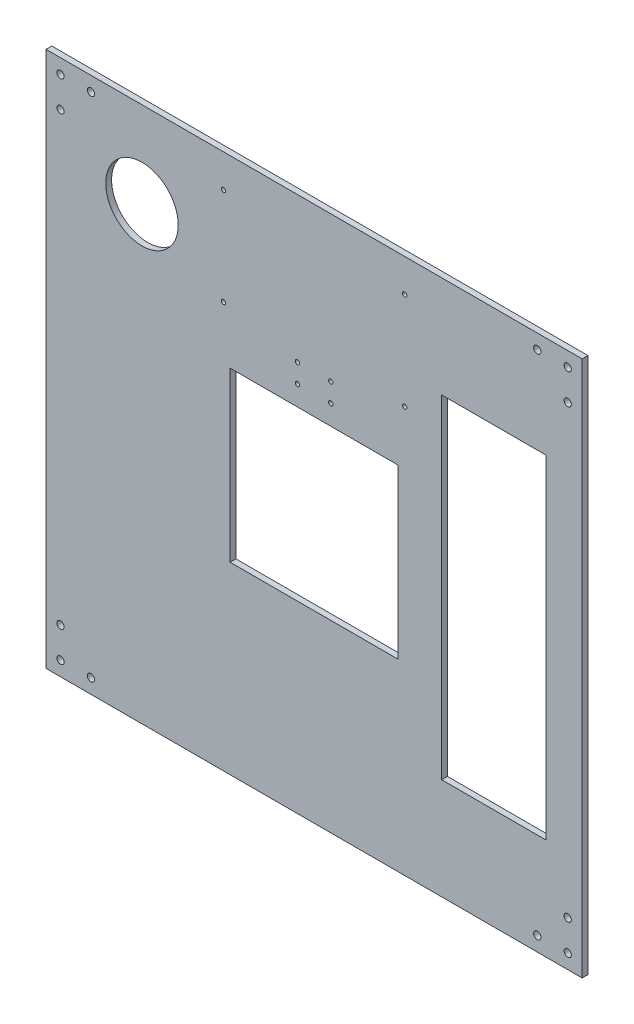
SolidWorks part; units mm, degrees
ref_plane "前视基准面" through (0, 0, 0) normal (0, 0, 1) x (1, 0, 0)
ref_plane "上视基准面" through (0, 0, 0) normal (0, 1, 0) x (1, 0, 0)
ref_plane "右视基准面" through (0, 0, 0) normal (1, 0, 0) x (0, 0, -1)
sketch "草图1" plane through (0, 0, 0) normal (0, 0, 1) x (1, 0, 0)
  line L1 (185, -185) -> (-185, -185)
  line L2 (185, -185) -> (185, 185)
  line L3 (185, 185) -> (-185, 185)
  line L4 (-185, -185) -> (-185, 185)
  line L5 (185, -185) -> (-185, 185) construction
  line L6 (185, 185) -> (-185, -185) construction
  point P0 (0, 0)
  dimension "D1" = 370
  dimension "D2" = 370
extrude "凸台-拉伸1" add sketch "草图1" along normal blind 4
sketch "草图2" plane through (0, 0, 4) normal (0, 0, 1) x (1, 0, 0)
  line L0 (-165, -175) -> (-154, -175) construction
  line L1 (-185, -185) -> (-165, -185) construction
  line L2 (-185, -185) -> (-185, -165) construction
  line L3 (-185, -165) -> (-165, -165) construction
  line L4 (-165, -185) -> (-165, -165) construction
  line L5 (-175, -165) -> (-175, -154) construction
  circle A0 centre (-175, -175) radius 2.5
  circle A1 centre (-154, -175) radius 2.5
  circle A2 centre (-175, -154) radius 2.5
  circle A3 centre (-154, 175) radius 2.5
  circle A4 centre (-175, 154) radius 2.5
  circle A5 centre (-175, 175) radius 2.5
  circle A6 centre (175, 154) radius 2.5
  circle A7 centre (154, 175) radius 2.5
  circle A8 centre (175, 175) radius 2.5
  circle A9 centre (154, -175) radius 2.5
  circle A10 centre (175, -154) radius 2.5
  circle A11 centre (175, -175) radius 2.5
  point P34 (0, 0)
  dimension "D3" = 10
  dimension "D4" = 10
  dimension "D5" = 5
  dimension "D6" = 11
  dimension "D7" = 5
  dimension "D9" = 5
  dimension "D1" = 20
  dimension "D2" = 20
  dimension "D8" = 11
  dimension "D10" = 4
extrude "切除-拉伸1" cut sketch "草图2" against normal through all
sketch "草图6" plane through (0, 0, 0) normal (0, 0, -1) x (-1, 0, 0)
  line L1 (62.5, 95.2498) -> (-62.5, 95.2498) construction
  line L2 (62.5, 95.2498) -> (62.5, 162.2498) construction
  line L3 (62.5, 162.2498) -> (-62.5, 162.2498) construction
  line L4 (-62.5, 95.2498) -> (-62.5, 162.2498) construction
  line L5 (62.5, 95.2498) -> (-62.5, 162.2498) construction
  line L6 (62.5, 162.2498) -> (-62.5, 95.2498) construction
  circle A0 centre (-62.5, 162.2498) radius 1.5
  circle A1 centre (-62.5, 95.2498) radius 1.5
  circle A2 centre (62.5, 95.2498) radius 1.5
  circle A3 centre (62.5, 162.2498) radius 1.5
  point P0 (0, 128.7498)
  dimension "D3" = 3
  dimension "D4" = 3
  dimension "D5" = 3
  dimension "D6" = 3
  dimension "D1" = 67
  dimension "D2" = 125
extrude "切除-拉伸7" cut sketch "草图6" against normal through all
sketch "草图7" plane through (0, 0, 0) normal (0, 0, -1) x (-1, 0, 0)
  circle A0 centre (118.7699, 125.6318) radius 25
  dimension "D1" = 50
extrude "切除-拉伸8" cut sketch "草图7" against normal through all
sketch "草图8" plane through (0, 0, 0) normal (0, 0, -1) x (-1, 0, 0)
  line L1 (58, -58) -> (-58, -58)
  line L2 (58, -58) -> (58, 58)
  line L3 (58, 58) -> (-58, 58)
  line L4 (-58, -58) -> (-58, 58)
  line L5 (58, -58) -> (-58, 58) construction
  line L6 (58, 58) -> (-58, -58) construction
  point P0 (0, 0)
  dimension "D1" = 116
  dimension "D2" = 116
extrude "切除-拉伸9" cut sketch "草图8" against normal blind 10
sketch "草图11" plane through (0, 0, 0) normal (0, 0, -1) x (-1, 0, 0)
  line L0 (0, 0) -> (-185, 0) construction
  line L1 (-185, -185) -> (-185, 185) construction
  line L3 (-88, -115) -> (-160, -115)
  line L4 (-88, -115) -> (-88, 115)
  line L5 (-88, 115) -> (-160, 115)
  line L6 (-160, -115) -> (-160, 115)
  line L7 (-88, -115) -> (-160, 115) construction
  line L8 (-88, 115) -> (-160, -115) construction
  line L9 (-58, 58) -> (-58, -58) construction
  point P5 (-124, 0)
  dimension "D1" = 30
  dimension "D2" = 230
  dimension "D3" = 25
extrude "切除-拉伸11" cut sketch "草图11" against normal blind 5
sketch "草图12" plane through (0, 0, 0) normal (0, 0, -1) x (-1, 0, 0)
  circle A0 centre (-11.5, 71.7321) radius 1.5
  circle A1 centre (11.5, 71.7321) radius 1.5
  circle A2 centre (-11.5, 84.7321) radius 1.5
  circle A3 centre (11.5, 84.7321) radius 1.5
extrude "切除-拉伸12" cut sketch "草图12" against normal through all
